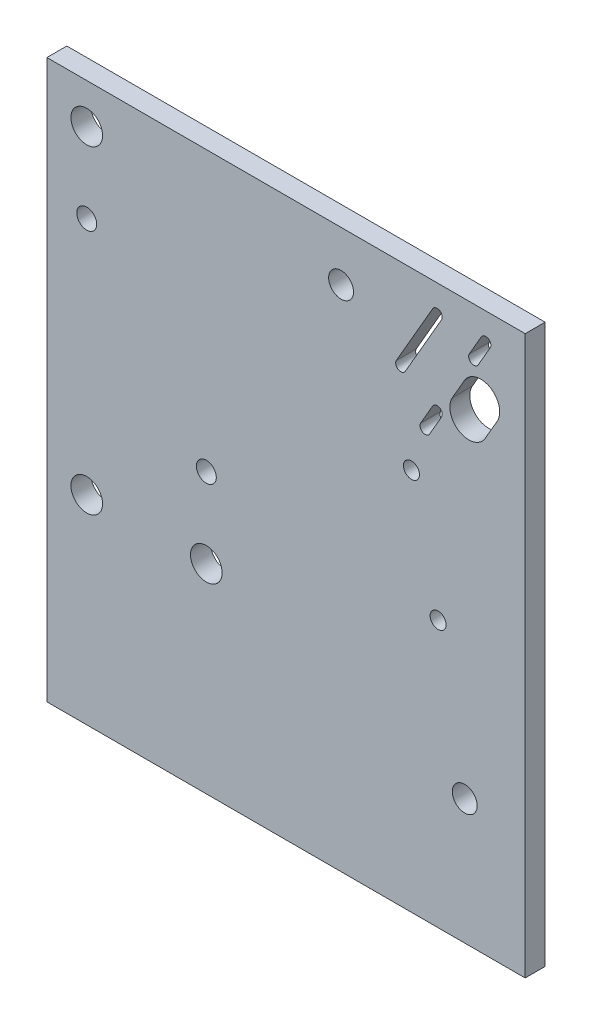
SolidWorks part; units mm, degrees
ref_plane "Front Plane" through (0, 0, 0) normal (1, 0, 0) x (0, 1, 0)
ref_plane "Top Plane" through (0, 0, 0) normal (0, 0, 1) x (0, 1, 0)
ref_plane "Right Plane" through (0, 0, 0) normal (0, 1, 0) x (-1, 0, 0)
sketch "Sketch2" plane through (0, 0, 0) normal (0, 0, 1) x (0, 1, 0)
  line L1 (0, 0) -> (177.8, 0)
  line L2 (0, 0) -> (0, 152.4)
  line L3 (0, 152.4) -> (177.8, 152.4)
  line L4 (177.8, 0) -> (177.8, 152.4)
  line L5 (63.5, 139.7) -> (165.1, 139.7) construction
  line L6 (63.5, 139.7) -> (63.5, 101.6) construction
  line L7 (63.5, 101.6) -> (165.1, 101.6) construction
  line L8 (165.1, 139.7) -> (165.1, 101.6) construction
  line L9 (63.5, 101.6) -> (124.236, 101.6) construction
  line L10 (63.5, 101.6) -> (63.5, 113.1176) construction
  line L11 (63.5, 113.1176) -> (124.236, 113.1176) construction
  line L12 (124.236, 101.6) -> (124.236, 113.1176) construction
  line L13 (63.5, 101.6) -> (139.7, 101.6) construction
  line L14 (63.5, 101.6) -> (63.5, 109.0554) construction
  line L15 (63.5, 109.0554) -> (139.7, 109.0554) construction
  line L16 (139.7, 101.6) -> (139.7, 109.0554) construction
  dimension "D2" = 12.7
  dimension "D3" = 12.7
  dimension "D4" = 38.1
  dimension "D5" = 177.8
  dimension "D6" = 152.4
  dimension "D7" = 11.5176
  dimension "D8" = 60.736
  dimension "D9" = 7.4554
  dimension "D10" = 76.2
  dimension "D11" = 101.6
extrude "Boss-Extrude1" add sketch "Sketch2" along normal blind 6.35
sketch "field_origin" plane through (0, 0, 0) normal (0, 0, -1) x (1, 0, 0)
  point P5 (-50.8, -222.25)
hole_wizard "3/8 Clearance Hole1" positions "Sketch3" profile "Sketch4" hole size "3/8" standard "ANSI Inch" end condition through all
sketch "Sketch3" plane through (0, 0, 6.35) normal (0, 0, 1) x (1, 0, 0)
  point P0 (-101.6, 63.5)
  point P3 (-139.7, 63.5)
  point P6 (-139.7, 165.1)
sketch "Sketch4" plane through (-101.6, 63.5, 6.35) normal (1, 0, 0) x (0, -1, 0)
  line L0 (0, 0) -> (0, 6.35)
  line L1 (0, 6.35) -> (5.0419, 6.35)
  line L2 (5.0419, 6.35) -> (5.0419, 0)
  line L5 (5.0419, 0) -> (0, 0)
  line L11 (0, -6.35) -> (0, 107.95) construction
  dimension "Thru Hole Dia." = 10.0838
  dimension "Thru Hole Depth" = 6.35
hole_wizard "Tap Drill for 1/4-20 Tap1" positions "Sketch7" profile "Sketch6" hole size "1/4-20" standard "ANSI Inch" end condition through all
sketch "Sketch7" plane through (0, 0, 6.35) normal (0, 0, 1) x (1, 0, 0)
  point P0 (-27.7546, 84.8487)
  point P3 (-36.2407, 122.0241)
  dimension "D1" = 100.2259
  dimension "D2" = 14.5593
  dimension "D3" = 137.4013
  dimension "D4" = 23.0454
sketch "Sketch6" plane through (-27.7546, 84.8487, 6.35) normal (1, 0, 0) x (0, -1, 0)
  line L0 (0, 0) -> (0, 6.35)
  line L1 (0, 6.35) -> (2.5527, 6.35)
  line L2 (2.5527, 6.35) -> (2.5527, 0)
  line L5 (2.5527, 0) -> (0, 0)
  line L11 (0, -6.35) -> (0, 107.95) construction
  dimension "Thru Hole Dia." = 5.1054
  dimension "Thru Hole Depth" = 6.35
sketch "Sketch8" plane through (0, 0, 6.35) normal (0, 0, 1) x (1, 0, 0)
  line L0 (-27.7546, 84.8487) -> (-152.4, -28.4904) construction
  line L1 (-36.2407, 122.0241) -> (-80.3848, 177.8) construction
  line L2 (0, 0) -> (0, 177.8) construction
  line L3 (-152.4, 177.8) -> (-152.4, 0) construction
  line L6 (0, 177.8) -> (-152.4, 177.8) construction
  line L7 (-87.3717, 30.6393) -> (-75.4292, 21.4295) construction
  line L8 (-30.8845, 115.2566) -> (-19.0589, 124.616) construction
  dimension "D1" = 38.36
  dimension "D2" = 47.72
  dimension "D3" = 15.0812
  dimension "D4" = 15.0812
sketch "Sketch13" plane through (0, 0, 0) normal (0, 0, -1) x (1, 0, 0)
  line L0 (-36.2407, -122.0241) -> (-145.707, -177.8) construction
  line L1 (0, -177.8) -> (-152.4, -177.8) construction
  line L2 (0, 0) -> (0, -177.8) construction
  line L3 (-70.1881, -139.3212) -> (-58.6567, -161.9527) construction
  line L4 (-27.7546, -84.8487) -> (-63.7707, 0) construction
  line L5 (-152.4, 0) -> (0, 0) construction
  line L6 (-42.6414, -49.7775) -> (-19.2606, -39.8529) construction
  point P8 (-58.6567, -161.9527)
  point P15 (-19.2606, -39.8529)
  point P18 (-58.6567, -161.9527)
  dimension "D1" = 63
  dimension "D2" = 23
  dimension "D3" = 25.4
  dimension "D4" = 38.1
  dimension "D5" = 25.4
  dimension "D6" = 38.1
hole_wizard "Tap Drill for 3/8-16 Tap3" positions "Sketch13" profile "Sketch16" hole size "3/8-16" standard "ANSI Inch" end condition through all
sketch "Sketch16" plane through (-58.6567, 161.9527, 0) normal (1, 0, 0) x (0, 1, 0)
  line L0 (0, 0) -> (0, 6.35)
  line L1 (0, 6.35) -> (3.9687, 6.35)
  line L2 (3.9687, 6.35) -> (3.9687, 0)
  line L5 (3.9687, 0) -> (0, 0)
  line L11 (0, -6.35) -> (0, 107.95) construction
  dimension "Thru Hole Dia." = 7.9375
  dimension "Thru Hole Depth" = 6.35
sketch "Sketch17" plane through (0, 0, 0) normal (0, 0, -1) x (1, 0, 0)
  line L0 (-139.7, -165.1) -> (-139.7, -139.7) construction
  line L1 (-139.7, -63.5) -> (-139.7, -165.1) construction
  line L3 (-139.7, -139.7) -> (-101.6, -139.7) construction
  line L4 (-139.7, -139.7) -> (-139.7, -88.9) construction
  line L5 (-139.7, -88.9) -> (-101.6, -88.9) construction
  line L6 (-101.6, -139.7) -> (-101.6, -88.9) construction
  point P1 (-139.7, -139.7)
  point P5 (-101.6, -88.9)
  dimension "D1" = 50.8
  dimension "D2" = 25.4
  dimension "D3" = 38.1
hole_wizard "1/4 (0.25) Diameter Hole1" positions "Sketch17" profile "Sketch18" hole size "1/4" standard "ANSI Inch" end condition through all
sketch "Sketch18" plane through (-101.6, 88.9, 0) normal (1, 0, 0) x (0, 1, 0)
  line L0 (0, 0) -> (0, 6.35)
  line L1 (0, 6.35) -> (3.175, 6.35)
  line L2 (3.175, 6.35) -> (3.175, 0)
  line L5 (3.175, 0) -> (0, 0)
  line L11 (0, -6.35) -> (0, 107.95) construction
  dimension "Thru Hole Dia." = 6.35
  dimension "Thru Hole Depth" = 6.35
sketch "Sketch19" plane through (0, 0, 0) normal (0, 0, -1) x (1, 0, 0)
  line L0 (-22.225, -152.4) -> (-10.6045, -145.6909) construction
  line L1 (-14.478, -165.8182) -> (-6.731, -152.4)
  line L2 (-6.731, -152.4) -> (-14.478, -138.9818)
  line L3 (-14.478, -138.9818) -> (-29.972, -138.9818)
  line L4 (-29.972, -138.9818) -> (-37.719, -152.4)
  line L5 (-37.719, -152.4) -> (-29.972, -165.8182)
  line L6 (-29.972, -165.8182) -> (-14.478, -165.8182)
  line L7 (0, -177.8) -> (-152.4, -177.8) construction
  line L8 (0, 0) -> (0, -177.8) construction
  circle A0 centre (-22.225, -152.4) radius 15.494 construction
  circle A1 centre (-16.0658, -148.844) radius 6.0325
  circle A2 centre (-22.225, -152.4) radius 18.415
  point P10 (0, 0)
  point P13 (-22.5437, -168.1559)
  point P14 (-25.7612, -138.1905)
  point P15 (-44.2224, -149.7843)
  point P16 (-33.192, -168.8895)
  point P17 (-37.4334, -150.5672)
  point P18 (-3.6612, -158.4081)
  point P23 (2.3207, -159.6827)
  point P26 (-17.8722, -157.9067)
  dimension "D3" = 12.065
  dimension "D4" = 36.83
  dimension "D1" = 7.112
  dimension "D2" = 30.988
  dimension "D5" = 25.4
  dimension "D6" = 22.225
  dimension "D7" = 0
sketch "Sketch20" plane through (0, 0, 0) normal (0, 0, -1) x (1, 0, 0)
  line L0 (-14.1608, -152.1436) -> (-17.9708, -145.5444) construction
  line L1 (-19.3851, -155.1598) -> (-23.1951, -148.5607)
  line L2 (-8.9365, -149.1273) -> (-12.7465, -142.5282)
  line L4 (-6.731, -152.4) -> (-14.478, -138.9818) construction
  arc A0 (-19.3851, -155.1598) -> (-8.9365, -149.1273) centre (-14.1608, -152.1436) ccw
  arc A1 (-12.7465, -142.5282) -> (-23.1951, -148.5607) centre (-17.9708, -145.5444) ccw
  circle A2 centre (-16.0658, -148.844) radius 6.0325 construction
  point P427 (-16.0658, -148.844)
  dimension "D1" = 7.62
sketch "Sketch22" plane through (0, 0, 0) normal (0, 0, -1) x (1, 0, 0)
  line L0 (-28.067, -142.2814) -> (-31.877, -135.6822) construction
  line L1 (-29.4803, -143.0973) -> (-33.2903, -136.4982)
  line L2 (-26.6537, -141.4654) -> (-30.4637, -134.8663)
  line L3 (-37.719, -152.4) -> (-29.972, -165.8182) construction
  line L4 (-28.067, -169.1178) -> (-39.624, -149.1004) construction
  line L5 (-29.4803, -169.9337) -> (-41.0373, -149.9164)
  line L6 (-26.6537, -168.3018) -> (-38.2107, -148.2845)
  line L7 (-12.573, -169.1178) -> (-16.383, -162.5186) construction
  line L8 (-13.9863, -169.9337) -> (-17.7963, -163.3346)
  line L9 (-11.1597, -168.3018) -> (-14.9697, -161.7027)
  arc A0 (-29.4803, -143.0973) -> (-26.6537, -141.4654) centre (-28.067, -142.2814) ccw
  arc A1 (-30.4637, -134.8663) -> (-33.2903, -136.4982) centre (-31.877, -135.6822) ccw
  arc A2 (-29.4803, -169.9337) -> (-26.6537, -168.3018) centre (-28.067, -169.1178) ccw
  arc A3 (-38.2107, -148.2845) -> (-41.0373, -149.9164) centre (-39.624, -149.1004) ccw
  arc A4 (-13.9863, -169.9337) -> (-11.1597, -168.3018) centre (-12.573, -169.1178) ccw
  arc A5 (-14.9697, -161.7027) -> (-17.7963, -163.3346) centre (-16.383, -162.5186) ccw
  point P0 (-33.8455, -159.1091)
  point P1 (-29.972, -138.9818)
  point P5 (-14.478, -165.8182)
  point P8 (-33.8455, -159.1091)
  point P12 (-29.972, -138.9818)
  point P25 (-14.478, -165.8182)
  point P31 (-36.8273, -157.1195)
  point P32 (-36.633, -157.456)
  dimension "D1" = 1.632
  dimension "D2" = 1.632
  dimension "D3" = 1.632
  dimension "D4" = 23.114
  dimension "D5" = 7.62
extrude "Cut-Extrude2" cut sketch "Sketch22" against normal through all
extrude "Cut-Extrude3" cut sketch "Sketch20" against normal through all
